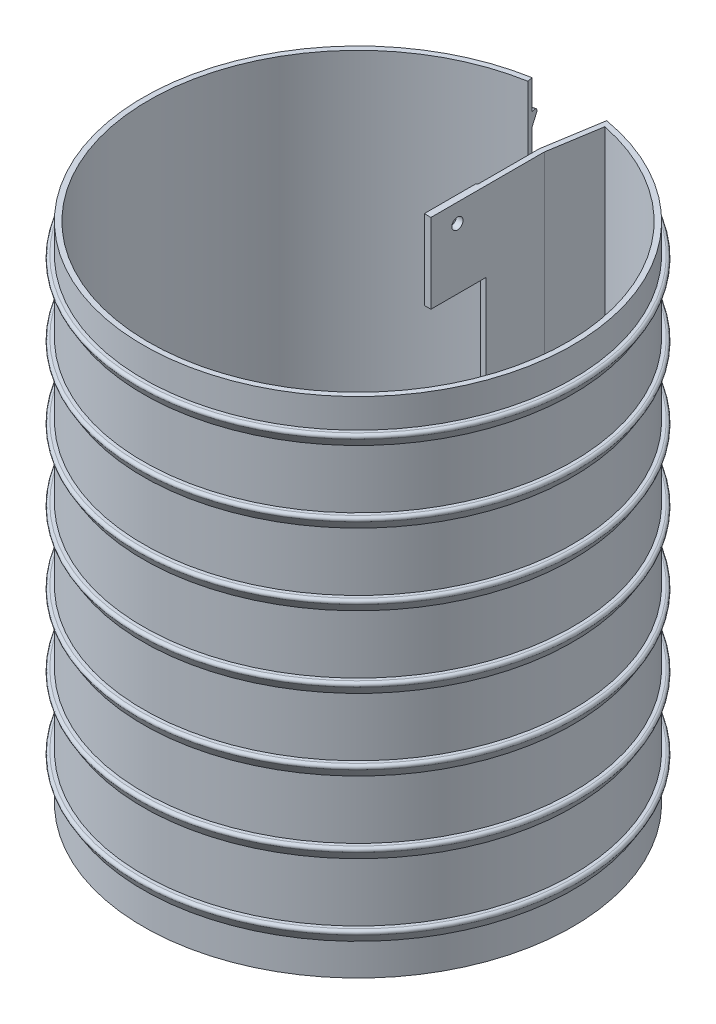
SolidWorks part; units mm, degrees
ref_plane "Plano frontal" through (0, 0, 0) normal (0, 0, 1) x (1, 0, 0)
ref_plane "Plano superior" through (0, 0, 0) normal (0, 1, 0) x (1, 0, 0)
ref_plane "Plano direito" through (0, 0, 0) normal (1, 0, 0) x (0, 0, -1)
sketch "Esboço1" plane through (0, 0, 0) normal (0, 1, 0) x (1, 0, 0)
  line L0 (0, 97.5906) -> (0, -93.5714) construction
  line L1 (-13.7182, 77.7998) -> (-14.0655, 79.7694)
  line L2 (13.7182, 77.7998) -> (14.0655, 79.7694)
  line L4 (12.5, 35.8) -> (12.5, 57.8)
  line L5 (10.5, 35.8) -> (10.5, 57.8)
  line L6 (10.5, 57.8) -> (13.7182, 77.7998)
  line L7 (12.5, 57.8) -> (15.6591, 77.4325)
  line L8 (12.5, 35.8) -> (10.5, 35.8)
  arc A0 (-14.0655, 79.7694) -> (14.0655, 79.7694) centre (0, 0) ccw
  arc A1 (-13.7182, 77.7998) -> (15.6591, 77.4325) centre (0, 0) ccw
  dimension "D1" = 10
  dimension "D3" = 81
  dimension "D4" = 79
  dimension "D2" = 10
  dimension "D5" = 2
  dimension "D6" = 1.9746
  dimension "D7" = 22
  dimension "D8" = 19.6325
extrude "Ressalto-extrusão1" add sketch "Esboço1" along normal blind 190
sketch "Esboço2" plane through (0, 0, 0) normal (0.9848, 0, -0.1736) x (-0.1736, 0, -0.9848)
  line L0 (81, 12) -> (81, 17)
  line L1 (81, 190) -> (81, 0) construction
  line L2 (81, 17) -> (82.2338, 17)
  line L3 (83.0913, 15.4855) -> (81, 12)
  line L4 (79, 0) -> (81, 0) construction
  arc A0 (82.2338, 17) -> (83.0913, 15.4855) centre (82.2338, 16) cw
  point P10 (84, 17)
  dimension "D4" = 1
  dimension "D1" = 3
  dimension "D2" = 17
  dimension "D3" = 5
ref_plane "Plano1" through (0, 13, 0) normal (0, 1, 0) x (1, 0, 0)
sketch "Esboço3" plane through (0, 13, 0) normal (0, 1, 0) x (1, 0, 0)
  arc A0 (-14.1523, 80.2618) -> (14.1523, 80.2618) centre (0, 0) ccw
  dimension "D1" = 163
sweep "Varredura1" add profiles "Esboço2" path "Esboço3"
pattern_linear "Padrão linear1" count 7 spacing 27 along (0, 1, 0) of "Varredura1"
sketch "Esboço4" plane through (0, 190, 0) normal (0, 1, 0) x (1, 0, 0)
  line L2 (10.5, 35.8) -> (10.5, 35)
  line L3 (10.5, 35) -> (10, 34.5)
  line L5 (10, 34.5) -> (10, 15)
  line L8 (12.5, 15) -> (12.5, 35.8)
  line L9 (10.5, 35.8) -> (12.5, 35.8)
  line L10 (10, 15) -> (12.5, 15)
extrude "Ressalto-extrusão2" add sketch "Esboço4" against normal blind 30
sketch "Esboço5" plane through (12.5, 0, 0) normal (1, 0, 0) x (0, 0, -1)
  line L2 (15, 190) -> (57.8, 190) construction
  line L6 (15, 160) -> (15, 190) construction
  circle A0 centre (25, 183) radius 2.1
  dimension "D1" = 4.2
  dimension "D2" = 10
  dimension "D3" = 7
extrude "Corte-extrusão1" cut sketch "Esboço5" against normal up to next contours A0
ref_plane "Plano2" through (-13.7182, 0, -77.7998) normal (0, -1, 0) x (-1, 0, 0)
